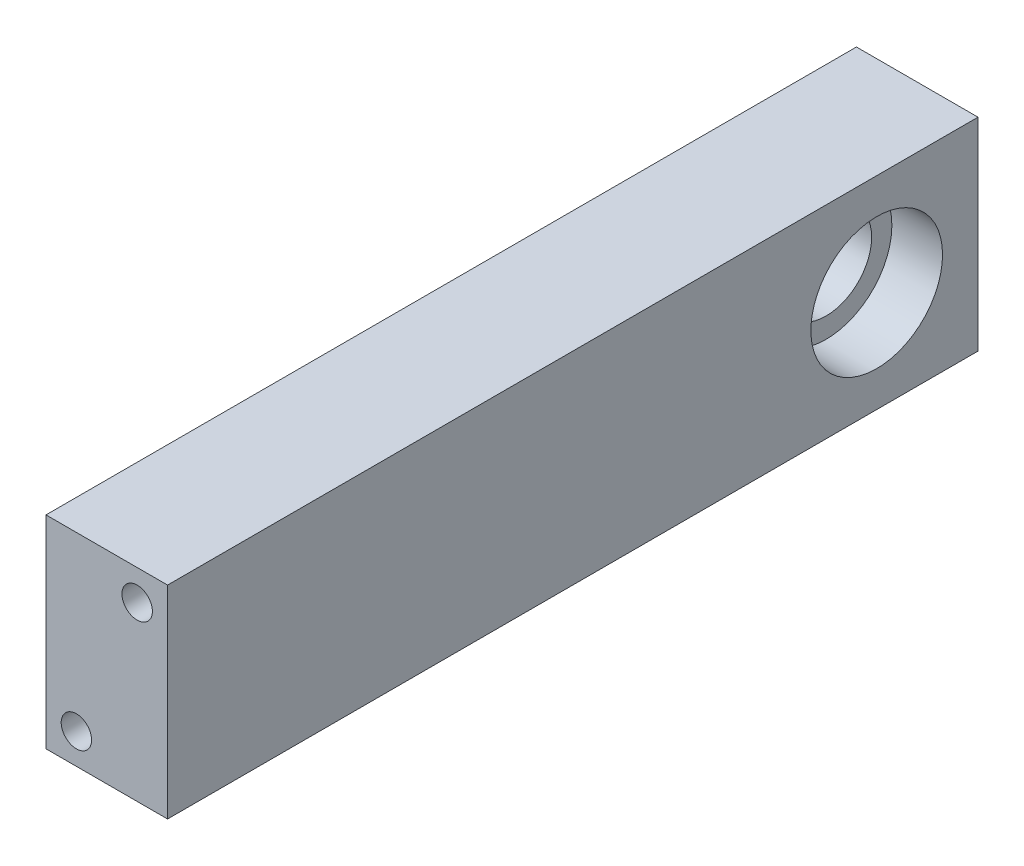
SolidWorks part; units mm, degrees
ref_plane "Płaszczyzna przednia" through (0, 0, 0) normal (0, 0, 1) x (1, 0, 0)
ref_plane "Płaszczyzna górna" through (0, 0, 0) normal (0, 1, 0) x (1, 0, 0)
ref_plane "Płaszczyzna prawa" through (0, 0, 0) normal (1, 0, 0) x (0, 0, -1)
sketch "Szkic1" plane through (0, 0, 0) normal (0, 0, 1) x (1, 0, 0)
  line L1 (-6, -10) -> (6, -10)
  line L2 (-6, -10) -> (-6, 10)
  line L3 (-6, 10) -> (6, 10)
  line L4 (6, -10) -> (6, 10)
  line L5 (-6, -10) -> (6, 10) construction
  line L6 (-6, 10) -> (6, -10) construction
  point P0 (0, 0)
  dimension "D1" = 20
  dimension "D2" = 12
extrude "Dodanie-wyciągnięcie1" add sketch "Szkic1" along normal blind 80
sketch "Szkic2" plane through (0, 0, 80) normal (0, 0, 1) x (1, 0, 0)
  line L0 (6, -10) -> (6, 10) construction
  line L3 (6, 10) -> (-6, 10) construction
  line L5 (-6, -10) -> (6, -10) construction
  line L6 (-6, 10) -> (-6, -10) construction
  circle A0 centre (3, 7) radius 1.5
  circle A1 centre (-3, -7) radius 1.5
  dimension "D1" = 3
  dimension "D2" = 3
  dimension "D3" = 3
  dimension "D4" = 3
  dimension "D5" = 3
  dimension "D6" = 3
extrude "Wytnij-wyciągnięcie1" cut sketch "Szkic2" against normal blind 10
sketch "Szkic5" plane through (6, 0, 0) normal (1, 0, 0) x (0, 0, -1)
  line L0 (-80, -10) -> (0, -10) construction
  line L1 (-80, -10) -> (-80, 10) construction
  circle A0 centre (-10, 0) radius 6.5
  dimension "D1" = 13
  dimension "D2" = 10
  dimension "D3" = 70
extrude "Wytnij-wyciągnięcie4" cut sketch "Szkic5" against normal blind 5
sketch "Szkic6" plane through (-6, 0, 0) normal (-1, 0, 0) x (0, 0, 1)
  line L0 (80, -10) -> (0, -10) construction
  line L1 (80, 10) -> (80, -10) construction
  circle A0 centre (10, 0) radius 4.5
  dimension "D1" = 9
  dimension "D2" = 10
  dimension "D3" = 70
extrude "Wytnij-wyciągnięcie5" cut sketch "Szkic6" against normal through all
